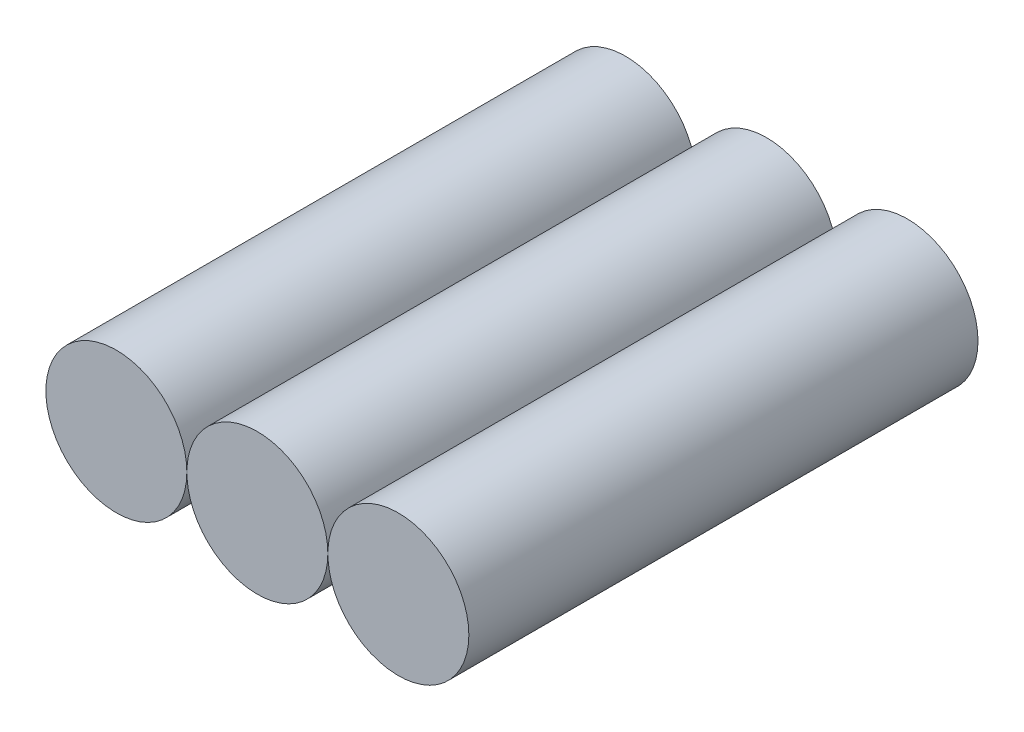
SolidWorks part; units mm, degrees
ref_plane "Ön Düzlem" through (0, 0, 0) normal (0, 0, 1) x (1, 0, 0)
ref_plane "Üst Düzlem" through (0, 0, 0) normal (0, 1, 0) x (1, 0, 0)
ref_plane "Sağ Düzlem" through (0, 0, 0) normal (1, 0, 0) x (0, 0, -1)
sketch "Çizim1" plane through (0, 0, 0) normal (0, 0, 1) x (1, 0, 0)
  circle A0 centre (-27.0322, 0) radius 9
  circle A1 centre (-9.0322, 0) radius 9
  circle A2 centre (8.9678, 0) radius 9
  dimension "D1" = 18
extrude "Yükseklik-Ekstrüzyon1" add sketch "Çizim1" along normal blind 65 contours A0 | A1 | A2 region at (-27.0322, 0, 0) region at (8.9678, 0, 0) region at (-9.0322, 0, 0)
